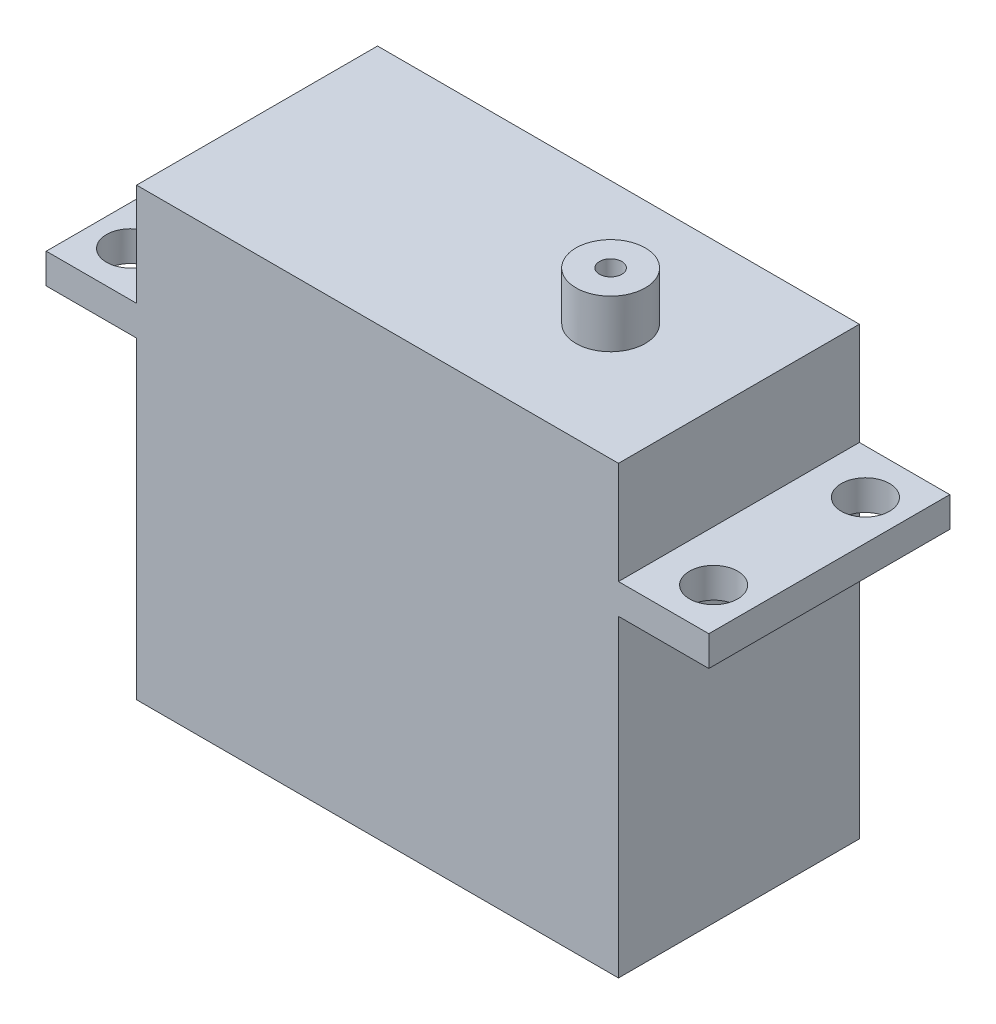
SolidWorks part; units mm, degrees
ref_plane "Front Plane" through (0, 0, 0) normal (0, 0, 1) x (1, 0, 0)
ref_plane "Top Plane" through (0, 0, 0) normal (0, 1, 0) x (1, 0, 0)
ref_plane "Right Plane" through (0, 0, 0) normal (1, 0, 0) x (0, 0, -1)
sketch "Sketch1" plane through (0, 0, 0) normal (0, 1, 0) x (1, 0, 0)
  line L1 (-20, -10) -> (20, -10)
  line L2 (-20, -10) -> (-20, 10)
  line L3 (-20, 10) -> (20, 10)
  line L4 (20, -10) -> (20, 10)
  line L5 (-20, -10) -> (20, 10) construction
  line L6 (-20, 10) -> (20, -10) construction
  point P0 (0, 0)
  dimension "D1" = 20
  dimension "D2" = 40
extrude "Boss-Extrude1" add sketch "Sketch1" along normal blind 37
ref_plane "Plane1" through (0, 26, 0) normal (0, 1, 0) x (1, 0, 0)
sketch "Sketch2" plane through (0, 26, 0) normal (0, 1, 0) x (1, 0, 0)
  line L0 (-20, -10) -> (20, -10) construction
  line L1 (20, 10) -> (27.5, 10)
  line L2 (20, 10) -> (20, -10)
  line L3 (20, -10) -> (27.5, -10)
  line L4 (27.5, 10) -> (27.5, -10)
  line L5 (0, -14.3) -> (0, 14.3) construction
  line L6 (-20, -10) -> (-27.5, -10)
  line L7 (-27.5, 10) -> (-27.5, -10)
  line L8 (-20, 10) -> (-27.5, 10)
  line L9 (-20, 10) -> (-20, -10)
  dimension "D1" = 7.5
extrude "Boss-Extrude2" add sketch "Sketch2" along normal blind 2.5
hole_wizard "Ø4.0 (4) Diameter Hole1" positions "Sketch3" profile "Sketch4" hole size "Ø4.0" standard "ANSI Metric" end condition through all
sketch "Sketch3" plane through (0, 28.5, 0) normal (0, 1, 0) x (1, 0, 0)
  line L1 (-24.2, 6.3) -> (24.2, 6.3) construction
  line L2 (-24.2, 6.3) -> (-24.2, -6.3) construction
  line L3 (-24.2, -6.3) -> (24.2, -6.3) construction
  line L4 (24.2, 6.3) -> (24.2, -6.3) construction
  line L5 (-27.5, 10) -> (-27.5, -10) construction
  line L6 (27.5, -10) -> (27.5, 10) construction
  line L7 (-27.5, 0) -> (27.5, 0) construction
  line L9 (-20, 10) -> (-27.5, 10) construction
  point P0 (-24.2, -6.3)
  point P2 (-24.2, 6.3)
  point P4 (24.2, 6.3)
  point P6 (24.2, -6.3)
  point P59 (-24.2, 0)
  dimension "D1" = 3.3
  dimension "D2" = 3.3
  dimension "D3" = 3.7
sketch "Sketch4" plane through (-24.2, 28.5, 6.3) normal (1, 0, 0) x (0, 0, 1)
  line L0 (0, 0) -> (0, 28.5)
  line L1 (0, 28.5) -> (2, 28.5)
  line L2 (2, 28.5) -> (2, 0)
  line L5 (2, 0) -> (0, 0)
  line L11 (0, -6.35) -> (0, 107.95) construction
  dimension "Thru Hole Dia." = 4
  dimension "Thru Hole Depth" = 28.5
sketch "Sketch5" plane through (0, 37, 0) normal (0, 1, 0) x (1, 0, 0)
  line L1 (-20, -10) -> (20, -10) construction
  line L2 (20, 10) -> (20, -10) construction
  circle A0 centre (9.625, -0.275) radius 2.875
  dimension "D1" = 5.75
  dimension "D2" = 9.725
  dimension "D3" = 10.375
extrude "Boss-Extrude3" add sketch "Sketch5" along normal blind 4
hole_wizard "Ø1.85 (1.85) Diameter Hole1" positions "Sketch6" profile "Sketch7" hole size "Ø1.85" standard "ANSI Metric"
sketch "Sketch6" plane through (0, 41, 0) normal (0, 1, 0) x (1, 0, 0)
  line L0 (9.625, 2.6) -> (9.625, -3.15) construction
  line L2 (6.75, -0.275) -> (12.5, -0.275) construction
  circle A0 centre (9.625, -0.275) radius 2.875 construction
  circle A1 centre (9.625, -0.275) radius 2.875 construction
  point P0 (9.625, -0.275)
  point P16 (9.625, -0.275)
sketch "Sketch7" plane through (9.625, 41, 0.275) normal (1, 0, 0) x (0, 0, 1)
  line L0 (0, 0) -> (0, 4.5558)
  line L1 (0, 4.5558) -> (0.925, 4)
  line L2 (0.925, 4) -> (0.925, 0)
  line L5 (0.925, 0) -> (0, 0)
  line L10 (0, 4.5558) -> (-0.925, 4) construction
  line L11 (0, -6.35) -> (0, 107.95) construction
  dimension "Hole Dia." = 1.85
  dimension "Hole Depth" = 4
  dimension "Drill Angle" = 118
equation "\"D1@Sketch2\"=(55-40)/2"
equation "\"D1@Sketch3\"=1.3 + 2"
equation "\"D2@Sketch3\"=\"D1@Sketch3\""
equation "\"D3@Sketch3\"= 1.7 + 2"
equation "\"D2@Sketch5\"=(\"D1@Sketch5\"/2) + 6.85"
equation "\"D3@Sketch5\"=(\"D1@Sketch5\"/2) + 7.5"
equation "\"D1@Boss-Extrude3\"=41-37mm"
